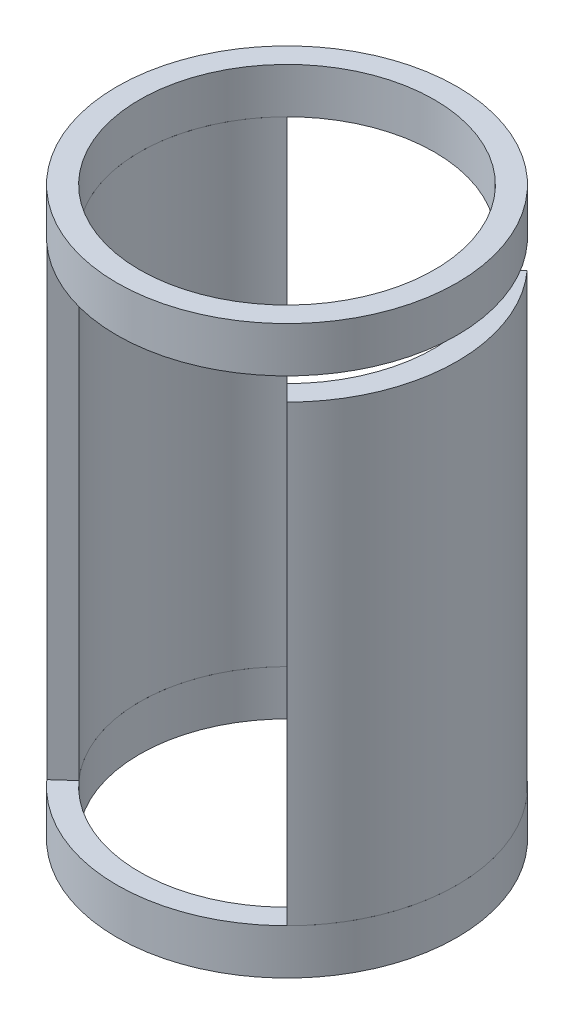
SolidWorks part; units mm, degrees
ref_plane "Front Plane" through (0, 0, 0) normal (0, 0, 1) x (1, 0, 0)
ref_plane "Top Plane" through (0, 0, 0) normal (0, 1, 0) x (1, 0, 0)
ref_plane "Right Plane" through (0, 0, 0) normal (1, 0, 0) x (0, 0, -1)
sketch "Sketch1" plane through (0, 0, 0) normal (0, 1, 0) x (1, 0, 0)
  line L0 (0, 0) -> (0, 13.8879) construction
  line L1 (0, 0) -> (12.9737, 0) construction
  line L2 (0, 0) -> (-7.7712, 7.7712) construction
  line L3 (0, 0) -> (26.9266, 26.9266) construction
  arc A0 (-5.3033, 5.3033) -> (-5.5736, -5.0185) centre (0, 0) ccw
  arc A1 (5.3033, -5.3033) -> (5.5736, 5.0185) centre (0, 0) ccw
  dimension "D1" = 7.5
  dimension "D3" = 7.5
  dimension "D2" = 87
  dimension "D4" = 87
extrude "Extrude-Thin1" add sketch "Sketch1" along normal blind 21 thin contours A0 | A1 thin type one direction reverse wall 1
sketch "Sketch5" plane through (0, 0, 0) normal (0, 1, 0) x (1, 0, 0)
  circle A0 centre (0, 0) radius 7.5
  dimension "D1" = 15
extrude "Extrude-Thin5" add sketch "Sketch5" against normal blind 2 separate body thin thin type one direction reverse wall 1
sketch3d "3DSketch3"
  circle A0 centre (0, 21, 0) radius 6.5
  circle A1 centre (0, 21, 0) radius 7.5
  point P2 (0, 28.5, 0)
  point P4 (0, 27.5, 0)
  dimension "D1" = 13
  dimension "D2" = 15
extrude "Boss-Extrude3" add sketch "3DSketch3" along direction (0, 1, 0) on the side of the normal blind 2 separate body
sketch "Sketch12" plane through (0, 21, 0) normal (0, 1, 0) x (1, 0, 0)
  arc A0 (4.8304, 4.3493) -> (4.5962, -4.5962) centre (0, 0) cw
  dimension "D1" = 6.5
  dimension "D2" = 87
extrude "Cut-Extrude1" cut sketch "Sketch12" against normal blind 1 and the other way through all
equation "\"Base_H\"=104"
